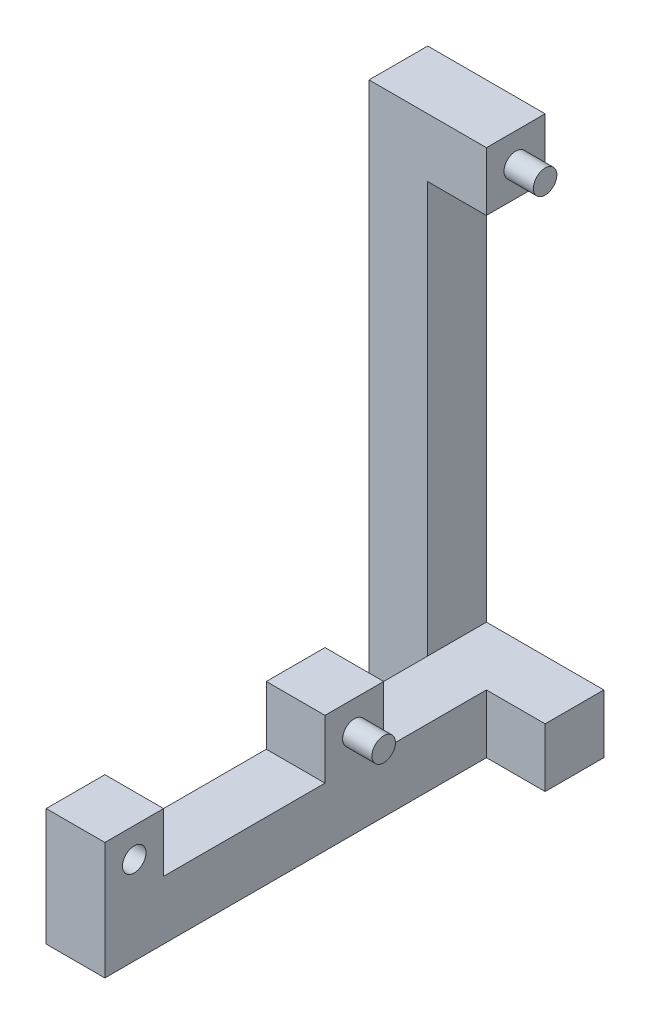
SolidWorks part; units mm, degrees
material "Hexcel AS4C (3000 Filaments)"
ref_plane "Front Plane" through (0, 0, 0) normal (0, 0, 1) x (1, 0, 0)
ref_plane "Top Plane" through (0, 0, 0) normal (0, 1, 0) x (1, 0, 0)
ref_plane "Right Plane" through (0, 0, 0) normal (1, 0, 0) x (0, 0, -1)
sketch "LowerBase" plane through (0, 0, 0) normal (1, 0, 0) x (0, 0, -1)
  line L9 (0, 0) -> (-1500, 0)
  line L10 (0, 0) -> (0, 200)
  line L11 (0, 200) -> (-1500, 200)
  line L12 (-1500, 0) -> (-1500, 200)
  line L13 (-1500, 200) -> (-1300, 200)
  line L14 (-1500, 200) -> (-1500, 400)
  line L15 (-1500, 400) -> (-1300, 400)
  line L16 (-1300, 200) -> (-1300, 400)
  line L17 (-750, 200) -> (-550, 200)
  line L18 (-750, 200) -> (-750, 400)
  line L19 (-750, 400) -> (-550, 400)
  line L20 (-550, 200) -> (-550, 400)
  dimension "D2" = 1500
  dimension "D1" = 200
  dimension "D3" = 200
  dimension "D4" = 200
  dimension "D5" = 200
  dimension "D6" = 200
  dimension "D7" = 550
  dimension "D8" = 550
extrude "Boss-Extrude1" add sketch "LowerBase" along normal blind 200 contours L12 L9 L10 L11 | L14 L15 L16 L13 | L19 L20 L17 L18
sketch "UpperBase" plane through (0, 0, 0) normal (1, 0, 0) x (0, 0, -1)
  line L1 (0, 0) -> (-200, 0)
  line L2 (0, 0) -> (0, 1800)
  line L3 (0, 1800) -> (-200, 1800)
  line L4 (-200, 0) -> (-200, 1800)
  dimension "D1" = 1800
  dimension "D2" = 200
extrude "Boss-Extrude2" add sketch "UpperBase" along direction (-1, 0, 0) on the side against the normal blind 200
sketch "TopPivot" plane through (0, 0, 0) normal (1, 0, 0) x (0, 0, -1)
  line L1 (-200, 1800) -> (0, 1800)
  line L2 (-200, 1800) -> (-200, 1600)
  line L3 (-200, 1600) -> (0, 1600)
  line L4 (0, 1800) -> (0, 1600)
  dimension "D1" = 200
  dimension "D2" = 200
extrude "Boss-Extrude3" add sketch "TopPivot" along normal blind 200
sketch "PressTable" plane through (0, 0, 0) normal (1, 0, 0) x (0, 0, -1)
  line L0 (0, 200) -> (-550, 200) construction
  line L1 (0, 0) -> (-200, 0)
  line L2 (0, 0) -> (0, 200)
  line L3 (0, 200) -> (-200, 200)
  line L4 (-200, 0) -> (-200, 200)
  dimension "D1" = 200
  dimension "D2" = 200
extrude "Boss-Extrude4" add sketch "PressTable" along normal blind 400
sketch "MiddleRivet" plane through (0, 0, 0) normal (1, 0, 0) x (0, 0, -1)
  line L0 (-750, 200) -> (-550, 400) construction
  circle A0 centre (-650, 300) radius 40
  dimension "D1" = 80
extrude "Boss-Extrude5" add sketch "MiddleRivet" along normal blind 300
sketch "TopRivet" plane through (0, 0, 0) normal (1, 0, 0) x (0, 0, -1)
  line L0 (0, 1800) -> (-200, 1600) construction
  circle A0 centre (-100, 1700) radius 40
  dimension "D1" = 80
extrude "Boss-Extrude6" add sketch "TopRivet" along normal blind 300
sketch "Sketch6" plane through (0, 0, 0) normal (1, 0, 0) x (0, 0, -1)
  line L0 (-1300, 400) -> (-1500, 200) construction
  line L1 (-1500, 0) -> (-1500, 400) construction
  circle A0 centre (-1400, 300) radius 40
  dimension "D1" = 80
extrude "Cut-Extrude1" cut sketch "Sketch6" against normal through all both and the other way through all
equation "\"baseFrameHeight\"= 180cm"
equation "\"baseFrameLength\"= 150cm"
equation "\"baseFrameThickness\"= 20cm"
equation "\"D2@LowerBase\" = \"baseFrameLength\""
equation "\"D1@LowerBase\" = \"baseFrameThickness\""
equation "\"D3@LowerBase\" = \"baseFrameThickness\""
equation "\"D4@LowerBase\" = \"baseFrameThickness\""
equation "\"D5@LowerBase\" = \"baseFrameThickness\""
equation "\"D6@LowerBase\" = \"baseFrameThickness\""
equation "\"D1@Boss-Extrude1\"=\"baseFrameThickness\""
equation "\"D1@UpperBase\" = \"baseFrameHeight\""
equation "\"D2@UpperBase\" = \"baseFrameThickness\""
equation "\"D1@Boss-Extrude2\"=\"baseFrameThickness\""
equation "\"D1@TopPivot\" = \"baseFrameThickness\""
equation "\"D2@TopPivot\" = \"baseFrameThickness\""
equation "\"D1@Boss-Extrude3\"=\"baseFrameThickness\""
equation "\"D2@PressTable\" = \"baseFrameThickness\""
equation "\"D1@Boss-Extrude4\"=2*\"baseFrameThickness\""
equation "\"D1@MiddleRivet\" = \"HoleMountDiameter@PrintingPress.Assembly\""
equation "\"D1@Boss-Extrude5\" = \"RivetLength@PrintingPress.Assembly\" + \"baseFrameThickness\""
equation "\"D1@TopRivet\" = \"HoleMountDiameter@PrintingPress.Assembly\""
equation "\"D1@Boss-Extrude6\" = \"RivetLength@PrintingPress.Assembly\" + \"baseFrameThickness\""
equation "\"D1@Sketch6\" = \"HoleMountDiameter@PrintingPress.Assembly\""
